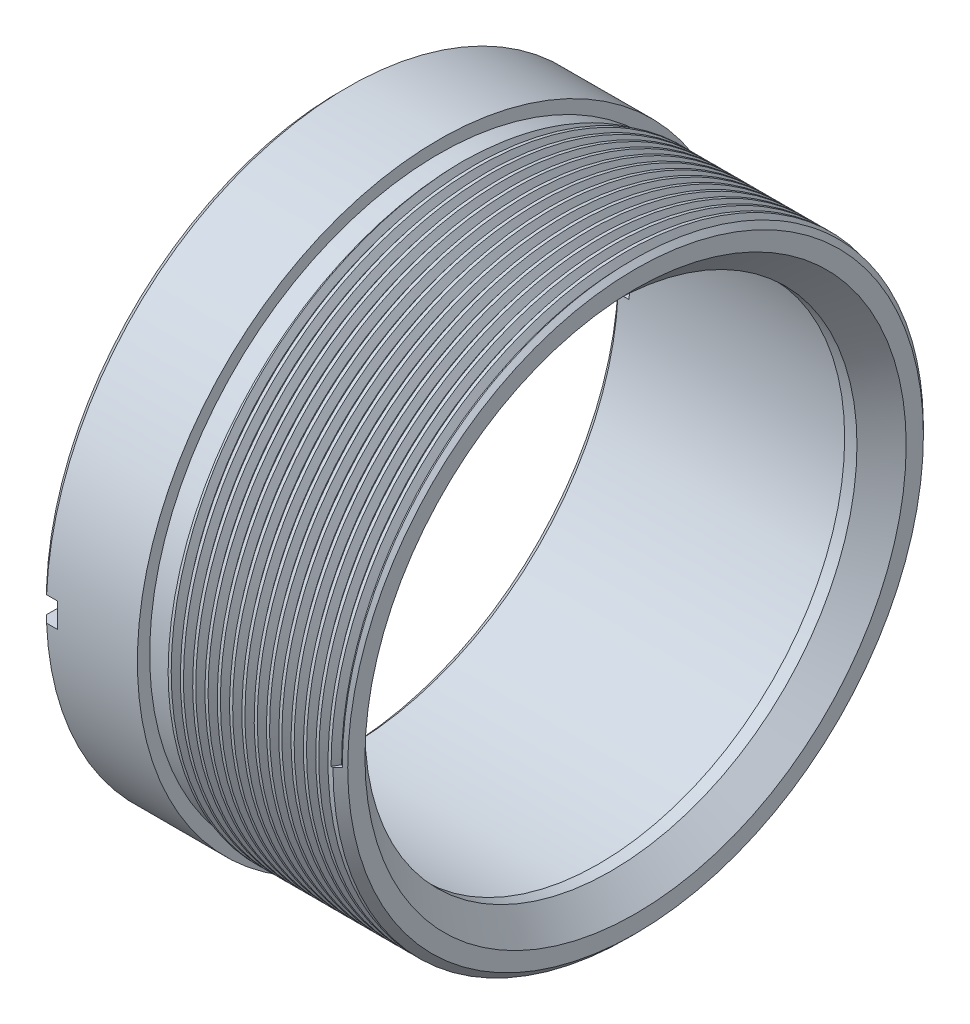
SolidWorks part; units mm, degrees
material "3.1325 (EN-AW 2017A)"
ref_plane "Front Plane" through (0, 0, 0) normal (0, 0, 1) x (1, 0, 0)
ref_plane "Top Plane" through (0, 0, 0) normal (0, 1, 0) x (1, 0, 0)
ref_plane "Right Plane" through (0, 0, 0) normal (1, 0, 0) x (0, 0, -1)
sketch "Sketch1" plane through (0, 0, 0) normal (0, 0, 1) x (1, 0, 0)
  line L0 (0, -11.3) -> (0, -11.95)
  line L2 (12, -11.7) -> (12, -11)
  line L4 (10.5, -10) -> (10.5, -11)
  line L5 (10.5, -11) -> (0.3, -11)
  line L6 (35.4703, 0) -> (-35.4703, 0) construction
  line L9 (10.5, -10) -> (11, -10)
  line L10 (0, -11.95) -> (0.3, -12.25)
  line L11 (11.7, -12) -> (12, -11.7)
  line L12 (12, -11) -> (11, -10)
  line L13 (0.3, -11) -> (0, -11.3)
  line L14 (0.3, -12.25) -> (4, -12.25)
  line L15 (4, -12.25) -> (4, -11.75)
  line L16 (4, -11.75) -> (5, -11.75)
  line L17 (5, -11.75) -> (5, -12)
  line L22 (5, -12) -> (11.7, -12)
  point P0 (0, -11)
  point P1 (0, -12.25)
  point P4 (12, -12)
  point P5 (12, -10)
  point P10 (0, 0)
  dimension "D2" = 22
  dimension "D3" = 12
  dimension "D4" = 1.5
  dimension "D5" = 0.25
  dimension "D6" = 1
  dimension "D7" = 20
  dimension "D8" = 0.3
  dimension "D9" = 45
  dimension "D13" = 8
  dimension "D17" = 24.5
  dimension "D18" = 24
revolve "Revolve1" add sketch "Sketch1" angle 360 about L6
cosmetic thread "Cosmetic Thread3" [suppressed] parameters "D2"=23.5
sketch "Sketch8" plane through (0, 0, 0) normal (-1, 0, 0) x (0, 0, 1)
  line L1 (12.25, -0.5) -> (-12.25, -0.5)
  line L2 (12.25, -0.5) -> (12.25, 0.5)
  line L3 (12.25, 0.5) -> (-12.25, 0.5)
  line L4 (-12.25, -0.5) -> (-12.25, 0.5)
  line L5 (12.25, -0.5) -> (-12.25, 0.5) construction
  line L6 (12.25, 0.5) -> (-12.25, -0.5) construction
  circle A0 centre (0, 0) radius 12.25 construction
  point P0 (0, 0)
  dimension "D1" = 1
extrude "Cut-Extrude1" cut sketch "Sketch8" against normal blind 0.75
thread "Thread3" pitch 0.5 method cut profile "Thread Profile3" start angle 0, offset 0, length 0, pitch 0.5, diameter 24
ref_plane "Plane3" through (12, 0, 12) normal (0, -1, 0) x (0, 0, 1)
sketch "Thread Profile3" plane through (12, 0, 12) normal (0, -1, 0) x (0, 0, 1)
  line L0 (0, 0) -> (0, 0.5) construction
  line L1 (0, 0.375) -> (-0.2706, 0.2188)
  line L2 (-0.2706, 0.2188) -> (-0.2706, 0.1563)
  line L3 (-0.2706, 0.1563) -> (0, 0)
  line L4 (-0.2706, 0.1875) -> (0, 0.1875) construction
  line L11 (0, 0.375) -> (0, 0)
  point P6 (0, 0)
  dimension "Pitch" = 0.5
  dimension "Profile_Angle" = 60
  dimension "Profile_Land" = 0.0625
  dimension "Profile_Height" = 0.2706
